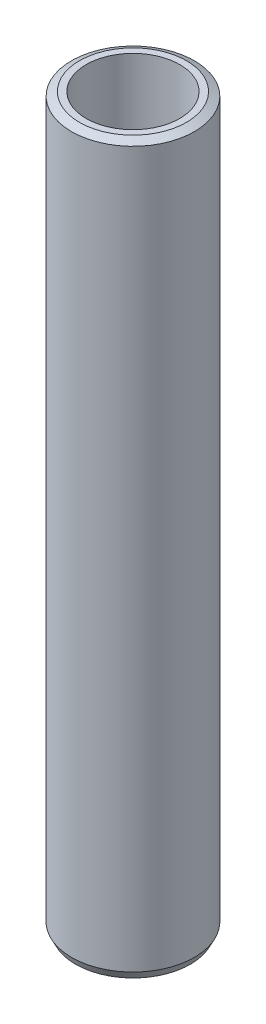
SolidWorks part; units mm, degrees
ref_plane "Front Plane" through (0, 0, 0) normal (0, 0, 1) x (1, 0, 0)
ref_plane "Top Plane" through (0, 0, 0) normal (0, 1, 0) x (1, 0, 0)
ref_plane "Right Plane" through (0, 0, 0) normal (1, 0, 0) x (0, 0, -1)
sketch "Sketch1" plane through (0, 0, 0) normal (0, 1, 0) x (1, 0, 0)
  circle A0 centre (0, 0) radius 50
  dimension "SHAFT_OD" = 100
extrude "Boss-Extrude1" add sketch "Sketch1" along normal blind 591.6949
sketch "Sketch2" plane through (0, 0, 0) normal (0, 1, 0) x (1, 0, 0)
  circle A0 centre (0, 0) radius 38.0547
  dimension "BORE_D" = 76.1094
extrude "Cut-Extrude1" cut sketch "Sketch2" along normal through all
chamfer "Chamfer1" distance 3.268 angle 63.27 2 edges at (0, 591.6949, 50) (0, 0, 50) first distance on face at (0, 591.6949, 50) first distance on face at (0, 0, 38.0547)
